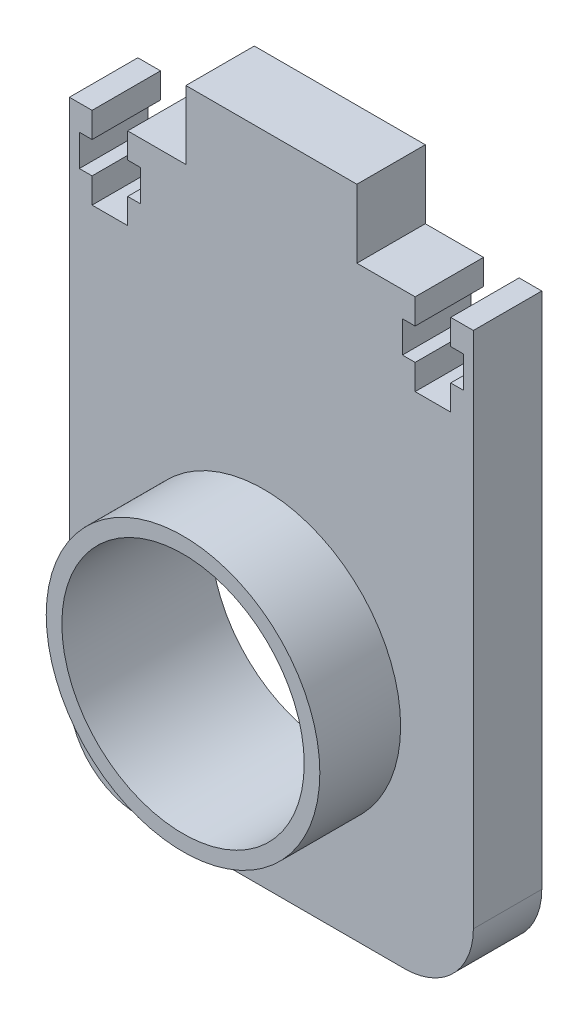
SolidWorks part; units mm, degrees
ref_plane "Front Plane" through (0, 0, 0) normal (0, 0, 1) x (1, 0, 0)
ref_plane "Top Plane" through (0, 0, 0) normal (0, 1, 0) x (1, 0, 0)
ref_plane "Right Plane" through (0, 0, 0) normal (1, 0, 0) x (0, 0, -1)
sketch "Sketch12" plane through (0, 0, 0) normal (0, 0, 1) x (1, 0, 0)
  line L0 (62.1258, 0) -> (62.1258, 121.71)
  line L1 (62.1258, 121.71) -> (137.1258, 121.71)
  line L2 (62.1258, 0) -> (137.1258, 0)
  line L3 (137.1258, 121.71) -> (137.1258, 0)
  line L4 (99.6258, 38.628) -> (99.6258, 121.71) construction
  circle A0 centre (99.6258, 38.628) radius 25.4
  circle A1 centre (99.6258, 38.628) radius 6.5
  dimension "D3" = 50.8
  dimension "D4" = 13
  dimension "D1" = 121.71
  dimension "D2" = 75
  dimension "D5" = 83.082
extrude "Boss-Extrude10" add sketch "Sketch12" along normal blind 12.7 separate body contours L1 L3 L2 L0
sketch "Sketch15" plane through (0, 0, 12.7) normal (0, 0, 1) x (1, 0, 0)
  circle A0 centre (98.2196, 38.6276) radius 25.4
  dimension "D1" = 50.8
extrude "Boss-Extrude11" add sketch "Sketch15" along normal blind 15
sketch "Sketch23" plane through (0, 0, 27.7) normal (0, 0, 1) x (1, 0, 0)
  circle A0 centre (98.2196, 38.6276) radius 22.5
  dimension "D1" = 45
extrude "Cut-Extrude7" cut sketch "Sketch23" against normal through all
fillet "Fillet2" radius 12.8 2 edges at (137.1258, 0, 6.35) (62.1258, 0, 6.35)
sketch "Sketch25" plane through (0, 0, 12.7) normal (0, 0, 1) x (1, 0, 0)
  line L0 (137.1258, 121.71) -> (137.1258, 109.01)
  line L1 (137.1258, 121.71) -> (137.1258, 12.8) construction
  line L2 (99.6258, 121.71) -> (99.6258, 98.7556)
  line L3 (62.1258, 12.8) -> (62.1258, 121.71) construction
  line L4 (62.1258, 109.01) -> (62.1258, 121.71)
  line L5 (115.5008, 109.01) -> (115.5008, 121.71)
  line L6 (62.1258, 121.71) -> (137.1258, 121.71) construction
  line L7 (115.5008, 121.71) -> (83.7508, 121.71)
  line L8 (83.7508, 121.71) -> (83.7508, 109.01)
  line L9 (83.7508, 109.01) -> (99.6258, 109.01)
  line L10 (99.6258, 109.01) -> (115.5008, 109.01)
  line L11 (137.1258, 109.01) -> (115.5008, 109.01)
  line L12 (115.5008, 121.71) -> (83.7508, 121.71)
  line L13 (83.7508, 109.01) -> (62.1258, 109.01)
  line M10 (137.1258, 12.8) -> (137.1258, 121.71)
  line M11 (137.1258, 121.71) -> (62.1258, 121.71)
  line M12 (62.1258, 121.71) -> (62.1258, 12.8)
  dimension "D1" = 12.7
  dimension "D2" = 31.75
extrude "Cut-Extrude9" cut sketch "Sketch25" against normal through all contours L13 L8 M11 M12 | L11 L5 M10 M11 region at (126.3133, 115.36, 12.7) region at (72.9383, 115.36, 12.7)
sketch "Sketch27" plane through (0, 0, 12.7) normal (0, 0, 1) x (1, 0, 0)
  line L0 (132.9173, 109.01) -> (132.9173, 104.311)
  line L1 (137.1258, 109.01) -> (115.5008, 109.01) construction
  line L2 (132.9173, 104.311) -> (135.2793, 104.311)
  line L3 (135.2793, 104.311) -> (135.2793, 98.469)
  line L4 (135.2793, 98.469) -> (132.9173, 98.469)
  line L5 (132.9173, 98.469) -> (132.9173, 93.77)
  line L6 (132.9173, 93.77) -> (126.3133, 93.77)
  line L7 (126.3133, 93.77) -> (126.3133, 98.469)
  line L8 (126.3133, 98.469) -> (123.9513, 98.469)
  line L9 (123.9513, 98.469) -> (123.9513, 104.311)
  line L10 (123.9513, 104.311) -> (126.3133, 104.311)
  line L11 (126.3133, 104.311) -> (126.3133, 109.01)
  line L12 (99.6258, 121.71) -> (99.6258, 67.6415) construction
  line L13 (83.7508, 121.71) -> (115.5008, 121.71) construction
  line L14 (72.9383, 98.469) -> (75.3003, 98.469)
  line L15 (75.3003, 98.469) -> (75.3003, 104.311)
  line L16 (75.3003, 104.311) -> (72.9383, 104.311)
  line L17 (72.9383, 104.311) -> (72.9383, 109.01)
  line L18 (66.3343, 109.01) -> (66.3343, 104.311)
  line L19 (66.3343, 104.311) -> (63.9723, 104.311)
  line L20 (63.9723, 104.311) -> (63.9723, 98.469)
  line L21 (63.9723, 98.469) -> (66.3343, 98.469)
  line L22 (66.3343, 98.469) -> (66.3343, 93.77)
  line L23 (66.3343, 93.77) -> (72.9383, 93.77)
  line L24 (72.9383, 93.77) -> (72.9383, 98.469)
  line L25 (132.9173, 109.01) -> (126.3133, 109.01)
  line L26 (72.9383, 109.01) -> (66.3343, 109.01)
  dimension "D1" = 6.604
  dimension "D2" = 11.328
  dimension "D3" = 15.24
  dimension "D4" = 5.842
ref_axis "Axis1" through (99.6258, 121.71, 12.7) along (0, -1, 0)
extrude "Cut-Extrude10" cut sketch "Sketch27" against normal through all
